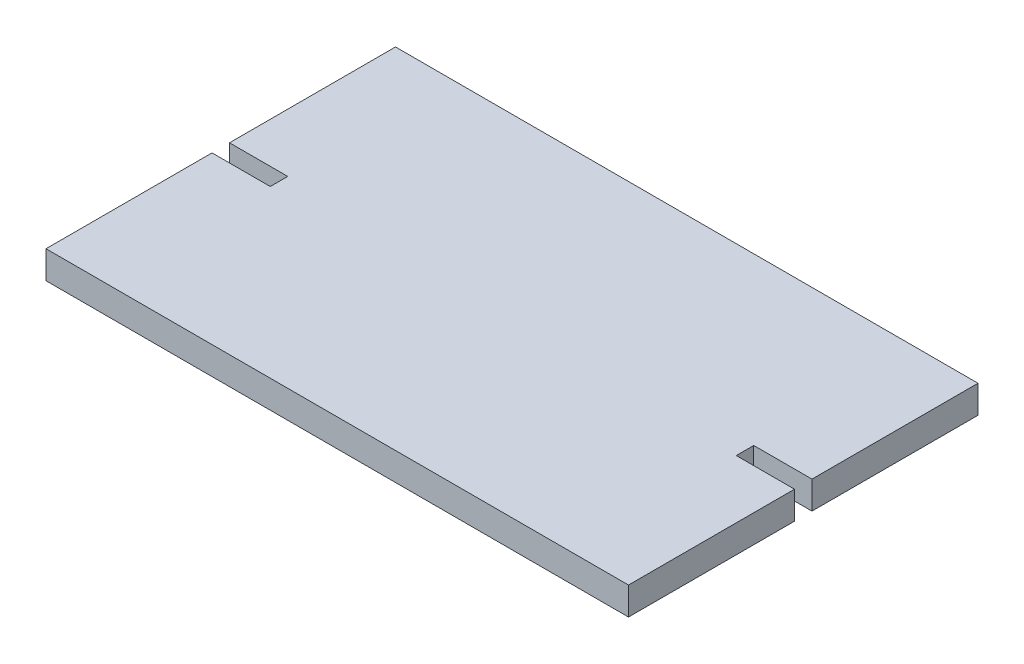
SolidWorks part; units mm, degrees
material "Hardboard"
ref_plane "Front Plane" through (0, 0, 0) normal (0, 0, 1) x (1, 0, 0)
ref_plane "Top Plane" through (0, 0, 0) normal (0, 1, 0) x (1, 0, 0)
ref_plane "Right Plane" through (0, 0, 0) normal (1, 0, 0) x (0, 0, -1)
sketch "Sketch3" plane through (0, 0, 0) normal (0, 1, 0) x (1, 0, 0)
  line L0 (0, -30) -> (0, 30) construction
  line L1 (-50, -30) -> (50, -30)
  line L2 (-50, 30) -> (-50, 1.5)
  line L3 (-50, 30) -> (50, 30)
  line L4 (40, 1.5) -> (40, -1.5)
  line L5 (-50, -30) -> (50, 30) construction
  line L6 (-50, 30) -> (50, -30) construction
  line L7 (-50, 1.5) -> (-40, 1.5)
  line L8 (-50, -1.5) -> (-50, -30)
  line L9 (-50, -1.5) -> (-40, -1.5)
  line L10 (-40, 1.5) -> (-40, -1.5)
  line L11 (50, -1.5) -> (40, -1.5)
  line L12 (50, -1.5) -> (50, -30)
  line L13 (50, 1.5) -> (40, 1.5)
  line L14 (50, 30) -> (50, 1.5)
  line L15 (-50, -1.5) -> (-50, 1.5) construction
  point P0 (0, 0)
  point P16 (-50, 0)
  point P17 (50, 0)
  dimension "D1" = 60
  dimension "D2" = 100
  dimension "D3" = 3
  dimension "D4" = 10
extrude "Boss-Extrude1" add sketch "Sketch3" along normal blind 4.7625
sketch "Sketch4" [suppressed] plane through (0, 0, 0) normal (1, 0, 0) x (0, 0, -1)
  line L0 (-30, 4.7625) -> (-1.5, 4.7625) construction
  line L1 (-30, 4.7625) -> (-30, 0) construction
  line L2 (-30, 0) -> (-1.5, 0) construction
  line L3 (-30, 4.7625) -> (-1.5, 4.7625)
  line L4 (-30, 4.7625) -> (-30, 0)
  line L5 (-30, 0) -> (-1.5, 0)
  line L6 (-30, 4.7625) -> (-30, -12.1326)
  line L7 (-30, -12.1326) -> (-9.7945, -32.8109)
  line L9 (-9.7945, -32.8109) -> (-7.1756, -30.2519)
  line L11 (-7.1756, -30.2519) -> (-24.8806, -12.1326)
  line L12 (-24.8806, -12.1326) -> (-24.8806, 4.7625)
  line L13 (-24.8806, 4.7625) -> (-30, 4.7625)
